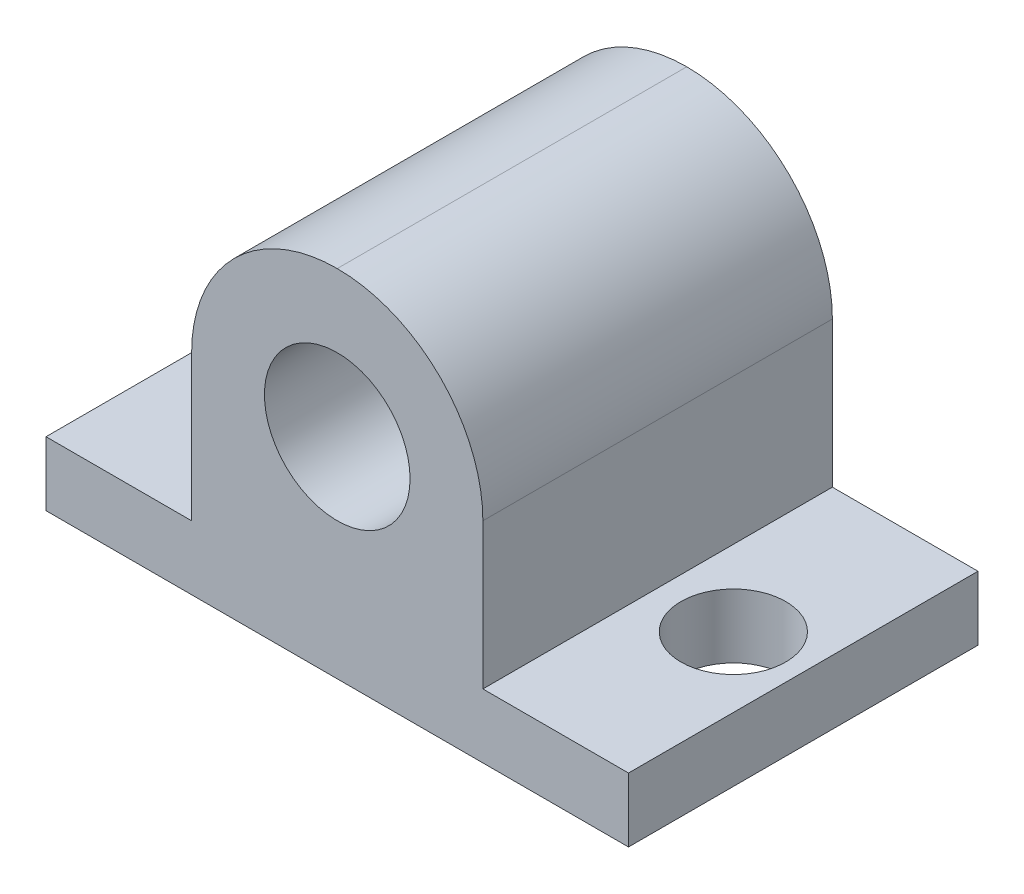
SolidWorks part; units mm, degrees
ref_plane "Front Plane" through (0, 0, 0) normal (0, 0, 1) x (1, 0, 0)
ref_plane "Top Plane" through (0, 0, 0) normal (0, 1, 0) x (1, 0, 0)
ref_plane "Right Plane" through (0, 0, 0) normal (1, 0, 0) x (0, 0, -1)
sketch "Sketch1" plane through (0, 0, 0) normal (0, 1, 0) x (1, 0, 0)
  line L1 (0, 0) -> (25.4, 0)
  line L2 (0, 0) -> (0, 15.24)
  line L3 (0, 15.24) -> (25.4, 15.24)
  line L4 (25.4, 0) -> (25.4, 15.24)
  dimension "D1" = 25.4
  dimension "D2" = 15.24
extrude "Boss-Extrude1" add sketch "Sketch1" along normal blind 2.794
sketch "Sketch2" plane through (0, 2.794, 0) normal (0, 1, 0) x (1, 0, 0)
  line L0 (25.4, 15.24) -> (0, 15.24) construction
  line L1 (6.35, 15.24) -> (19.05, 15.24)
  line L2 (6.35, 15.24) -> (6.35, 0)
  line L3 (6.35, 0) -> (19.05, 0)
  line L4 (19.05, 15.24) -> (19.05, 0)
  line L5 (0, 0) -> (25.4, 0) construction
  line L6 (0, 15.24) -> (6.35, 15.24) construction
  line L7 (19.05, 15.24) -> (25.4, 15.24) construction
  dimension "D1" = 12.7
extrude "Boss-Extrude2" add sketch "Sketch2" along normal blind 12.7
fillet "Fillet1" radius 6.35 2 edges at (6.35, 15.494, -7.62) (19.05, 15.494, -7.62)
sketch "Sketch3" plane through (0, 0, 0) normal (0, 0, 1) x (1, 0, 0)
  circle A0 centre (12.7, 9.144) radius 3.175
  dimension "D1" = 6.35
extrude "Cut-Extrude1" cut sketch "Sketch3" against normal through all
sketch "Sketch4" plane through (0, 2.794, 0) normal (0, 1, 0) x (1, 0, 0)
  line L0 (6.35, 15.24) -> (0, 15.24) construction
  line L3 (25.4, 15.24) -> (19.05, 15.24) construction
  line L5 (12.7, 0) -> (12.7, 15.24) construction
  circle A0 centre (3.048, 7.62) radius 2.286
  circle A1 centre (22.352, 7.62) radius 2.286
  dimension "D5" = 4.572
  dimension "D1" = 7.62
  dimension "D2" = 7.62
  dimension "D3" = 9.652
  dimension "D4" = 9.652
extrude "Cut-Extrude2" cut sketch "Sketch4" against normal through all
